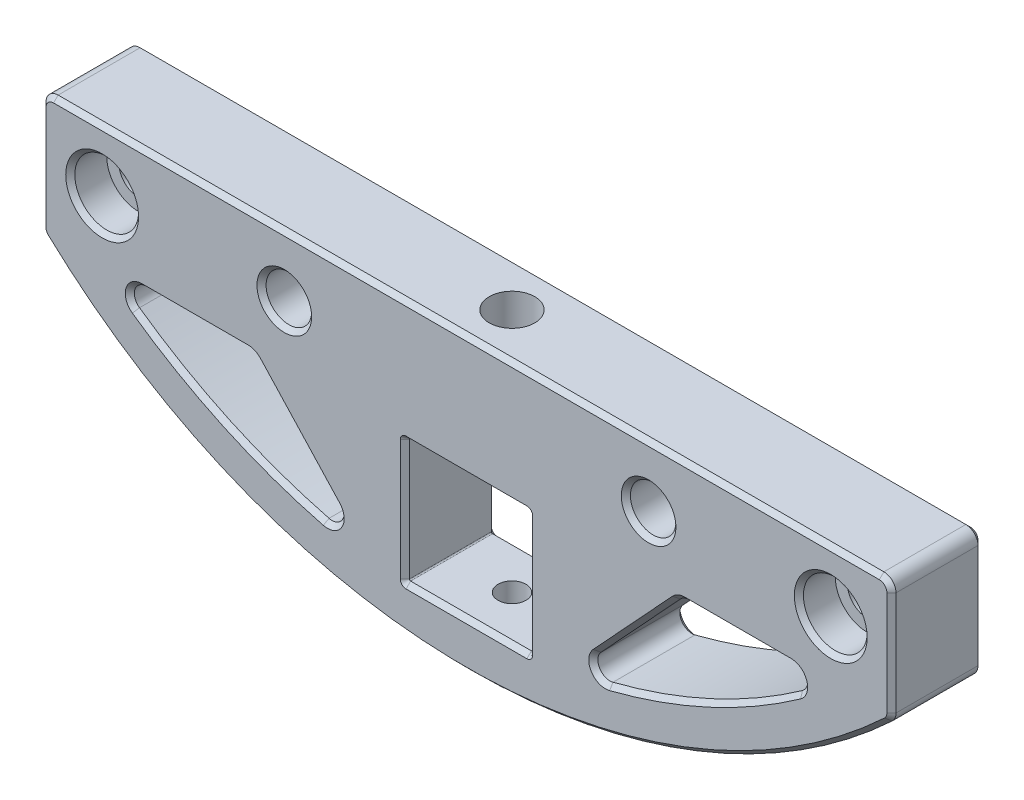
SolidWorks part; units mm, degrees
note: The reader was unsure of these and kept them because the rebuilt part matched: shared geometry of "Skizze4<3>".
ref_plane "Front" through (0, 0, 0) normal (0, 0, 1) x (1, 0, 0)
ref_plane "Top" through (0, 0, 0) normal (0, 1, 0) x (1, 0, 0)
ref_plane "Right" through (0, 0, 0) normal (1, 0, 0) x (0, 0, -1)
sketch "Skizze3" plane through (0, 0, 0) normal (0, 0, 1) x (1, 0, 0)
  line L0 (0, 0) -> (0, 40) construction
  line L1 (-70, 20) -> (70, 20)
  line L2 (50, 20) -> (-50, 20) construction
  line L3 (70, 20) -> (70, 0)
  line L4 (-70, 20) -> (-70, 0)
  line L5 (10, -20) -> (3, -20) construction
  line L6 (-10.15, 0) -> (10.15, 0)
  line L7 (50, 0) -> (-50, 0) construction
  line L8 (10.15, 0) -> (10.15, -20.3)
  line L9 (10.15, -20.3) -> (0.05, -20.3)
  line L10 (-10.15, -20.3) -> (0.05, -20.3)
  line L11 (-10.15, 0) -> (-10.15, -20.3)
  line L12 (-60, 20) -> (-60, 4.0983) construction
  line L13 (-39.0891, 10) -> (0, 10) construction
  line L15 (-50, 10) -> (-50, 13) construction
  line L16 (17.097, -19.4405) -> (35.0807, 0)
  line L17 (35.0807, 0) -> (59.397, 0)
  line L18 (-17.097, -19.4405) -> (-35.0807, 0)
  line L19 (-35.0807, 0) -> (-59.397, 0)
  arc A0 (70, 0) -> (0, -28) centre (0, 73.5) cw
  arc A1 (-70, 0) -> (0, -28) centre (0, 73.5) ccw
  circle A2 centre (-60, 10) radius 3.25
  circle A3 centre (60, 10) radius 3.25
  circle A4 centre (-30, 10) radius 2.3
  circle A5 centre (30, 10) radius 2.3
  arc A6 (59.397, 0) -> (17.097, -19.4405) centre (0, 73.5) cw
  arc A7 (-59.397, 0) -> (-17.097, -19.4405) centre (0, 73.5) ccw
  point P13 (0, 20)
  dimension "D7" = 6.5
  dimension "D10" = 4.6
  dimension "D4" = 7
  dimension "D1" = 140
  dimension "D2" = 8
  dimension "D3" = 20
  dimension "D5" = 20.3
  dimension "D6" = 10
  dimension "D8" = 10
  dimension "D9" = 10
  dimension "D11" = 20
  dimension "D12" = 20
  dimension "D13" = 7
extrude "Aufsatz-Linear austragen1" add sketch "Skizze3" along normal blind 15
sketch "Skizze4" plane through (0, 0, 15) normal (0, 0, 1) x (1, 0, 0)
  line L0 (0, 0) -> (0, 26.2298) construction
  line L1 (10.15, 0) -> (-10.15, 0) construction
  circle A0 centre (-30, 10) radius 3.75
  circle A1 centre (30, 10) radius 3.75
  circle A2 centre (-60, 10) radius 5.25
  circle A3 centre (60, 10) radius 5.25
  circle M12 centre (-60, 10) radius 3.25
  circle M13 centre (60, 10) radius 3.25
  circle M14 centre (-30, 10) radius 2.3
  circle M15 centre (30, 10) radius 2.3
  dimension "D1" = 7.5
  dimension "D2" = 10.5
extrude "Schnitt-Linear austragen1" cut sketch "Skizze4" against normal offset from surface (8 mm away) 7 contours A0 M14 | A1 M15 up to face at (-27.7, 10, 0)
extrude "Schnitt-Linear austragen2" cut sketch "Skizze4<3>" against normal offset from surface (6 mm away) 9 contours A2 M12 | A3 M13 up to face at (-27.7, 10, 0)
sketch "Skizze4<3>" plane through (0, 0, 15) normal (0, 0, 1) x (1, 0, 0) same geometry as "Skizze4"
sketch "Skizze5" plane through (0, 0, 0) normal (0, 1, 0) x (1, 0, 0)
  line L0 (0, 0) -> (0, -15) construction
  line L1 (70, -15) -> (-70, -15) construction
  circle A0 centre (0, -7.5) radius 2.3
  dimension "D1" = 4.6
extrude "Schnitt-Linear austragen3" cut sketch "Skizze5" against normal through all and the other way through all
sketch "Skizze7" plane through (0, 0, 0) normal (0, 1, 0) x (1, 0, 0)
  circle A0 centre (0, -7.5) radius 3.75
  dimension "D1" = 7.5
extrude "Schnitt-Linear austragen4" cut sketch "Skizze7" along normal through all from offset 7
sketch "Skizze8" plane through (0, -20.3, 0) normal (0, 1, 0) x (1, 0, 0)
  circle A0 centre (0, -7.5) radius 3.75
  dimension "D1" = 7.5
extrude "Schnitt-Linear austragen5" cut sketch "Skizze8" against normal blind 7 from offset 7 offset against normal yes
fillet "Verrundung1" radius 2 4 edges at (-70, 20, 7.5) (-70, 0, 7.5) (70, 0, 7.5) (70, 20, 7.5)
fillet "Verrundung2" radius 0.2 4 edges at (10.15, 0, 7.5) (-10.15, 0, 7.5) (-10.15, -20.3, 7.5) (10.15, -20.3, 7.5)
fillet "Verrundung3" radius 2 6 edges at (17.097, -19.4405, 7.5) (35.0807, 0, 7.5) (59.397, 0, 7.5) (-17.097, -19.4405, 7.5) (-59.397, 0, 7.5) (-35.0807, 0, 7.5)
chamfer "Fase1" distance 0.75 angle 45 64 edges at (-21.1722, -17.1464, 0) (-39.653, -12.2781, 0) (-55.3475, -1.3937, 0) (-44.6983, 0, 0) (-35.1539, -0.1675, 0) (-27.9546, -7.7033, 0) (55.3475, -1.3937, 0) (39.653, -12.2781, 0) (21.1722, -17.1464, 0) (27.9546, -7.7033, 0) (35.1539, -0.1675, 0) (44.6983, 0, 0) (27.7, 10, 0) (56.75, 10, 0) (-10.0914, -0.0586, 0) (0, 0, 0) (10.0914, -0.0586, 0) (10.15, -10.15, 0) (10.0914, -20.2414, 0) (0, -20.3, 0) (-10.0914, -20.2414, 0) (-10.15, -10.15, 0) (-69.8349, 0.0665, 0) (0, -28, 0) (69.8349, 0.0665, 0) (70, 9.4311, 0) (69.4142, 19.4142, 0) (0, 20, 0) (-69.4142, 19.4142, 0) (-70, 9.4311, 0) (-56.75, 10, 0) (-27.7, 10, 0) (65.25, 10, 15) (-26.25, 10, 15) (-21.1722, -17.1464, 15) (-27.9546, -7.7033, 15) (-35.1539, -0.1675, 15) (-44.6983, 0, 15) (-55.3475, -1.3937, 15) (-39.653, -12.2781, 15) (10.0914, -0.0586, 15) (0, 0, 15) (-10.0914, -0.0586, 15) (-10.15, -10.15, 15) (-10.0914, -20.2414, 15) (0, -20.3, 15) (10.0914, -20.2414, 15) (10.15, -10.15, 15) (69.4142, 19.4142, 15) (70, 9.4311, 15) (69.8349, 0.0665, 15) (0, -28, 15) (-69.8349, 0.0665, 15) (-70, 9.4311, 15) (-69.4142, 19.4142, 15) (0, 20, 15) (55.3475, -1.3937, 15) (44.6983, 0, 15) (35.1539, -0.1675, 15) (27.9546, -7.7033, 15) (21.1722, -17.1464, 15) (39.653, -12.2781, 15) (33.75, 10, 15) (-54.75, 10, 15)
fillet "Verrundung4" radius 1 1 edges at (3.6501, -27.9343, 6.6403)
